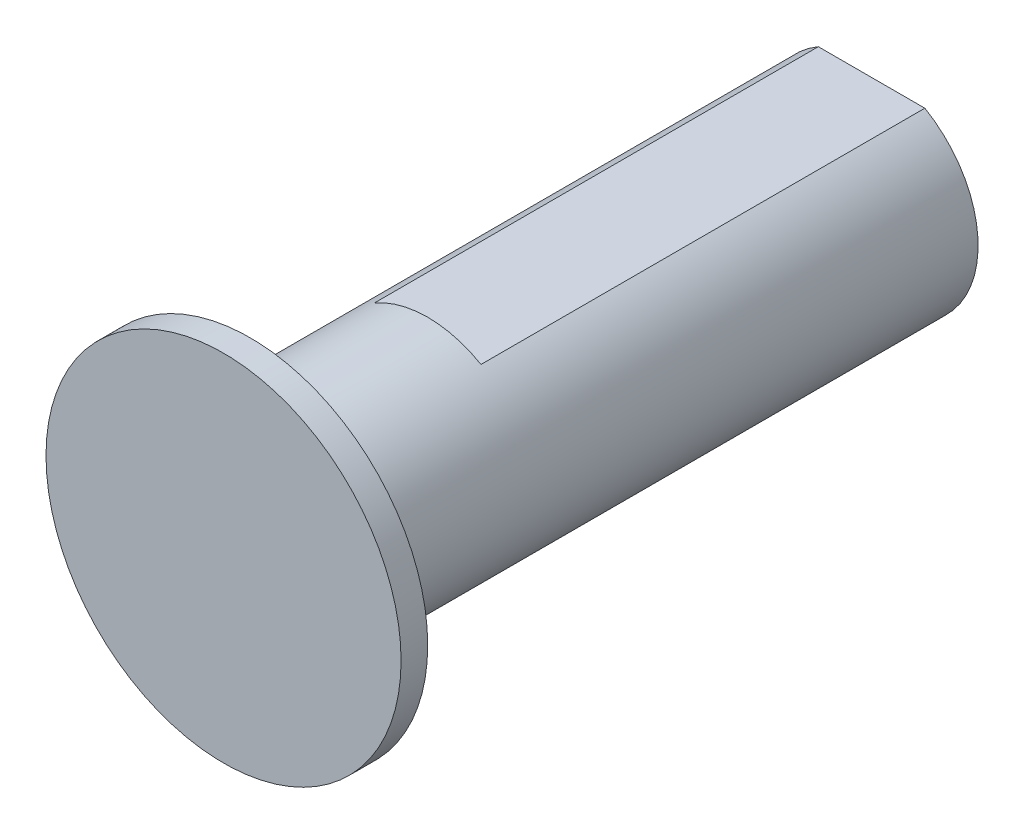
SolidWorks part; units mm, degrees
ref_plane "Front Plane" through (0, 0, 0) normal (0, 0, 1) x (1, 0, 0)
ref_plane "Top Plane" through (0, 0, 0) normal (0, 1, 0) x (1, 0, 0)
ref_plane "Right Plane" through (0, 0, 0) normal (1, 0, 0) x (0, 0, -1)
sketch "Sketch1" plane through (0, 0, 0) normal (0, 0, 1) x (1, 0, 0)
  line L0 (-3, 5.1962) -> (3, 5.1962)
  circle A0 centre (0, 0) radius 6
  dimension "D1" = 12
  dimension "D2" = 6
extrude "Boss-Extrude1" add sketch "Sketch1" along normal blind 35 contours A0
sketch "Sketch2" plane through (0, 0, 0) normal (0, 0, -1) x (-1, 0, 0)
  line L0 (-3, 5.1962) -> (3, 5.1962)
  circle A1 centre (0, 0) radius 6 construction
  circle A2 centre (0, 0) radius 6
  circle M3 centre (0, 0) radius 6
  dimension "D1" = 6
extrude "Cut-Extrude1" cut sketch "Sketch2" against normal blind 25 contours L0 M3 region at (0, 5.5196, 0)
sketch "Sketch3" plane through (0, 0, 35) normal (0, 0, 1) x (1, 0, 0)
  circle A0 centre (0, 0) radius 10
  dimension "D1" = 20
extrude "Boss-Extrude2" add sketch "Sketch3" along normal blind 1.5
